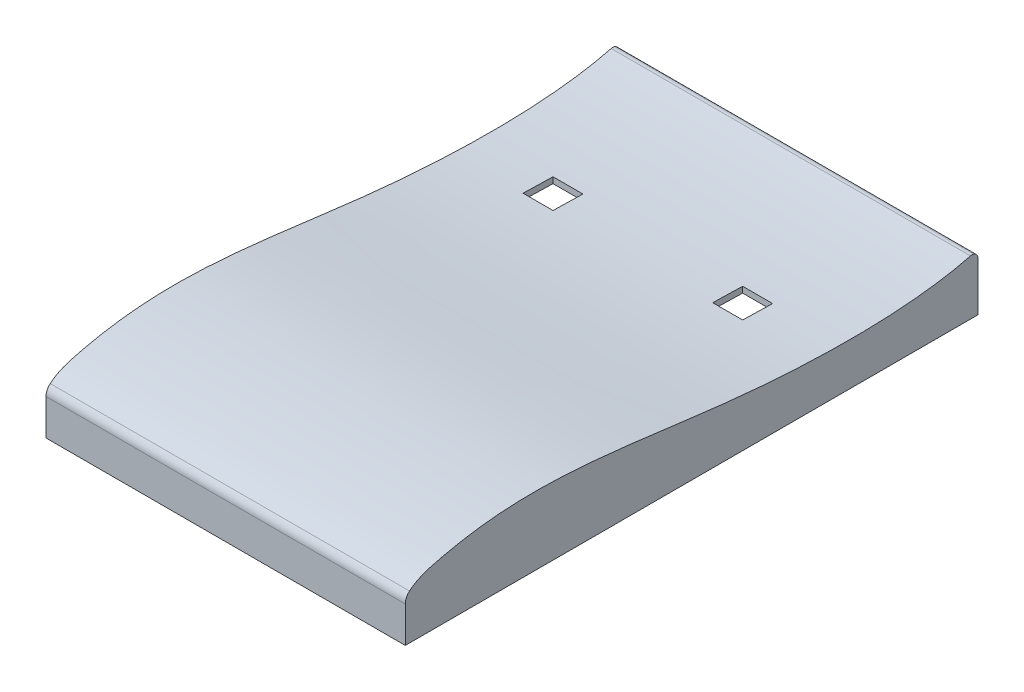
SolidWorks part; units mm, degrees
ref_plane "정면" through (0, 0, 0) normal (0, 0, 1) x (1, 0, 0)
ref_plane "윗면" through (0, 0, 0) normal (0, 1, 0) x (1, 0, 0)
ref_plane "우측면" through (0, 0, 0) normal (1, 0, 0) x (0, 0, -1)
sketch "스케치6" plane through (0, 0, 0) normal (1, 0, 0) x (0, 0, -1)
  line L0 (0, 0) -> (0, -6)
  line L1 (0, -6) -> (95.6347, -6)
  line L2 (95.6347, -6) -> (95.6347, 2.1754)
  line L3 (-22.0513, 0) -> (22.0513, 0) construction
  line L4 (0, -10.5081) -> (0, 10.5081) construction
  arc A0 (94.3801, 3.1425) -> (95.6347, 2.1754) centre (94.6347, 2.1754) cw
  arc A1 (0.7028, 1.5223) -> (0, 0) centre (2, 0) ccw
  spline S0 degree 3 poles (0.7028, 1.5223) (1.9876, 2.617) (15.7997, 6.7046) (31.0763, 5.2425) (65.7348, 0.6027) (84.4769, 0.536) (94.3801, 3.1425) knots 0.002177 0.002177 0.002177 0.002177 0.049494 0.428561 0.517585 0.939729 0.939729 0.939729 0.939729
  point P6 (0, 0)
  point P13 (0, 0)
  point P17 (0, 0)
  dimension "D1" = 2
  dimension "D2" = 1
  dimension "D3" = 95.6347
  dimension "D4" = 6
extrude "보스-돌출2" add sketch "스케치6" along normal blind 60
shell "쉘3" thickness 1 removed face at (30, -6, -47.8173)
sketch "스케치7" plane through (0, -6, 0) normal (0, -1, 0) x (1, 0, 0)
  line L0 (30, 0) -> (30, -95.6347) construction
  line L1 (11.6647, -73) -> (16.6647, -73)
  line L2 (11.6647, -73) -> (11.6647, -68)
  line L3 (11.6647, -68) -> (16.6647, -68)
  line L4 (16.6647, -73) -> (16.6647, -68)
  line L5 (60, 0) -> (0, 0) construction
  line L6 (60, -95.6347) -> (0, -95.6347) construction
  line L7 (48.3353, -68) -> (43.3353, -68)
  line L8 (48.3353, -73) -> (48.3353, -68)
  line L9 (48.3353, -73) -> (43.3353, -73)
  line L10 (43.3353, -73) -> (43.3353, -68)
  line L11 (0, 0) -> (0, -95.6347) construction
  dimension "D1" = 5
  dimension "D2" = 5
  dimension "D3" = 11.6647
  dimension "D4" = 68
extrude "컷-돌출3" cut sketch "스케치7" against normal blind 60
